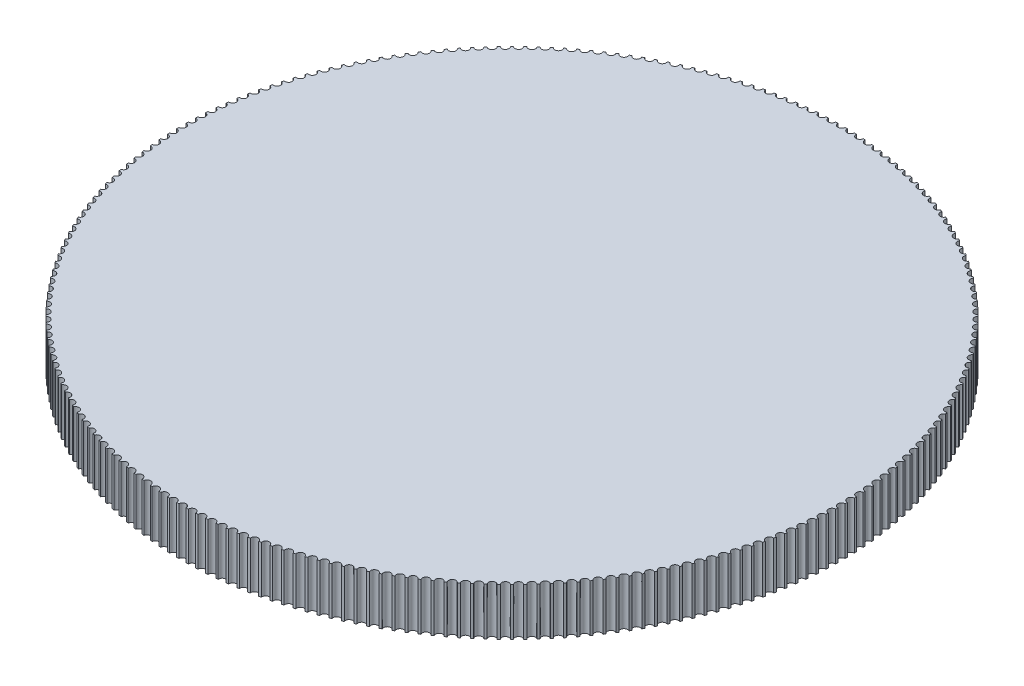
SolidWorks part; units mm, degrees
ref_plane "Front Plane" through (0, 0, 0) normal (0, 0, 1) x (1, 0, 0)
ref_plane "Top Plane" through (0, 0, 0) normal (0, 1, 0) x (1, 0, 0)
ref_plane "Right Plane" through (0, 0, 0) normal (1, 0, 0) x (0, 0, -1)
sketch "Sketch1" plane through (0, 0, 0) normal (0, 1, 0) x (1, 0, 0)
  line L0 (-69.255, 0) -> (69.255, 0) construction
  circle A0 centre (0, 0) radius 69.255
  dimension "D1" = 138.51
extrude "Boss-Extrude1" add sketch "Sketch1" along normal blind 10
sketch "Sketch2" plane through (0, 10, 0) normal (0, 1, 0) x (1, 0, 0)
  line L0 (0, 0) -> (69.255, 0) construction
  circle A0 centre (0, 0) radius 69.255 construction
  circle A1 centre (69.255, 0) radius 0.755
  circle A2 centre (69.2268, -1.9776) radius 0.755
  circle A3 centre (69.1421, -3.9537) radius 0.755
  circle A4 centre (69.001, -5.9265) radius 0.755
  circle A5 centre (68.8036, -7.8945) radius 0.755
  circle A6 centre (68.5501, -9.856) radius 0.755
  circle A7 centre (68.2407, -11.8095) radius 0.755
  circle A8 centre (67.8756, -13.7534) radius 0.755
  circle A9 centre (67.4552, -15.686) radius 0.755
  circle A10 centre (66.9798, -17.6059) radius 0.755
  circle A11 centre (66.4497, -19.5114) radius 0.755
  circle A12 centre (65.8654, -21.401) radius 0.755
  circle A13 centre (65.2274, -23.2731) radius 0.755
  circle A14 centre (64.5362, -25.1262) radius 0.755
  circle A15 centre (63.7924, -26.9589) radius 0.755
  circle A16 centre (62.9966, -28.7696) radius 0.755
  circle A17 centre (62.1493, -30.5568) radius 0.755
  circle A18 centre (61.2514, -32.319) radius 0.755
  circle A19 centre (60.3035, -34.055) radius 0.755
  circle A20 centre (59.3065, -35.7631) radius 0.755
  circle A21 centre (58.261, -37.4421) radius 0.755
  circle A22 centre (57.1681, -39.0905) radius 0.755
  circle A23 centre (56.0285, -40.7071) radius 0.755
  circle A24 centre (54.8432, -42.2904) radius 0.755
  circle A25 centre (53.6132, -43.8393) radius 0.755
  circle A26 centre (52.3394, -45.3524) radius 0.755
  circle A27 centre (51.023, -46.8285) radius 0.755
  circle A28 centre (49.665, -48.2664) radius 0.755
  circle A29 centre (48.2664, -49.665) radius 0.755
  circle A30 centre (46.8285, -51.023) radius 0.755
  circle A31 centre (45.3524, -52.3394) radius 0.755
  circle A32 centre (43.8393, -53.6132) radius 0.755
  circle A33 centre (42.2904, -54.8432) radius 0.755
  circle A34 centre (40.7071, -56.0285) radius 0.755
  circle A35 centre (39.0905, -57.1681) radius 0.755
  circle A36 centre (37.4421, -58.261) radius 0.755
  circle A37 centre (35.7631, -59.3065) radius 0.755
  circle A38 centre (34.055, -60.3035) radius 0.755
  circle A39 centre (32.319, -61.2514) radius 0.755
  circle A40 centre (30.5568, -62.1493) radius 0.755
  circle A41 centre (28.7696, -62.9966) radius 0.755
  circle A42 centre (26.9589, -63.7924) radius 0.755
  circle A43 centre (25.1262, -64.5362) radius 0.755
  circle A44 centre (23.2731, -65.2274) radius 0.755
  circle A45 centre (21.401, -65.8654) radius 0.755
  circle A46 centre (19.5114, -66.4497) radius 0.755
  circle A47 centre (17.6059, -66.9798) radius 0.755
  circle A48 centre (15.686, -67.4552) radius 0.755
  circle A49 centre (13.7534, -67.8756) radius 0.755
  circle A50 centre (11.8095, -68.2407) radius 0.755
  circle A51 centre (9.856, -68.5501) radius 0.755
  circle A52 centre (7.8945, -68.8036) radius 0.755
  circle A53 centre (5.9265, -69.001) radius 0.755
  circle A54 centre (3.9537, -69.1421) radius 0.755
  circle A55 centre (1.9776, -69.2268) radius 0.755
  circle A56 centre (0, -69.255) radius 0.755
  circle A57 centre (-1.9776, -69.2268) radius 0.755
  circle A58 centre (-3.9537, -69.1421) radius 0.755
  circle A59 centre (-5.9265, -69.001) radius 0.755
  circle A60 centre (-7.8945, -68.8036) radius 0.755
  circle A61 centre (-9.856, -68.5501) radius 0.755
  circle A62 centre (-11.8095, -68.2407) radius 0.755
  circle A63 centre (-13.7534, -67.8756) radius 0.755
  circle A64 centre (-15.686, -67.4552) radius 0.755
  circle A65 centre (-17.6059, -66.9798) radius 0.755
  circle A66 centre (-19.5114, -66.4497) radius 0.755
  circle A67 centre (-21.401, -65.8654) radius 0.755
  circle A68 centre (-23.2731, -65.2274) radius 0.755
  circle A69 centre (-25.1262, -64.5362) radius 0.755
  circle A70 centre (-26.9589, -63.7924) radius 0.755
  circle A71 centre (-28.7696, -62.9966) radius 0.755
  circle A72 centre (-30.5568, -62.1493) radius 0.755
  circle A73 centre (-32.319, -61.2514) radius 0.755
  circle A74 centre (-34.055, -60.3035) radius 0.755
  circle A75 centre (-35.7631, -59.3065) radius 0.755
  circle A76 centre (-37.4421, -58.261) radius 0.755
  circle A77 centre (-39.0905, -57.1681) radius 0.755
  circle A78 centre (-40.7071, -56.0285) radius 0.755
  circle A79 centre (-42.2904, -54.8432) radius 0.755
  circle A80 centre (-43.8393, -53.6132) radius 0.755
  circle A81 centre (-45.3524, -52.3394) radius 0.755
  circle A82 centre (-46.8285, -51.023) radius 0.755
  circle A83 centre (-48.2664, -49.665) radius 0.755
  circle A84 centre (-49.665, -48.2664) radius 0.755
  circle A85 centre (-51.023, -46.8285) radius 0.755
  circle A86 centre (-52.3394, -45.3524) radius 0.755
  circle A87 centre (-53.6132, -43.8393) radius 0.755
  circle A88 centre (-54.8432, -42.2904) radius 0.755
  circle A89 centre (-56.0285, -40.7071) radius 0.755
  circle A90 centre (-57.1681, -39.0905) radius 0.755
  circle A91 centre (-58.261, -37.4421) radius 0.755
  circle A92 centre (-59.3065, -35.7631) radius 0.755
  circle A93 centre (-60.3035, -34.055) radius 0.755
  circle A94 centre (-61.2514, -32.319) radius 0.755
  circle A95 centre (-62.1493, -30.5568) radius 0.755
  circle A96 centre (-62.9966, -28.7696) radius 0.755
  circle A97 centre (-63.7924, -26.9589) radius 0.755
  circle A98 centre (-64.5362, -25.1262) radius 0.755
  circle A99 centre (-65.2274, -23.2731) radius 0.755
  circle A100 centre (-65.8654, -21.401) radius 0.755
  circle A101 centre (-66.4497, -19.5114) radius 0.755
  circle A102 centre (-66.9798, -17.6059) radius 0.755
  circle A103 centre (-67.4552, -15.686) radius 0.755
  circle A104 centre (-67.8756, -13.7534) radius 0.755
  circle A105 centre (-68.2407, -11.8095) radius 0.755
  circle A106 centre (-68.5501, -9.856) radius 0.755
  circle A107 centre (-68.8036, -7.8945) radius 0.755
  circle A108 centre (-69.001, -5.9265) radius 0.755
  circle A109 centre (-69.1421, -3.9537) radius 0.755
  circle A110 centre (-69.2268, -1.9776) radius 0.755
  circle A111 centre (-69.255, 0) radius 0.755
  circle A112 centre (-69.2268, 1.9776) radius 0.755
  circle A113 centre (-69.1421, 3.9537) radius 0.755
  circle A114 centre (-69.001, 5.9265) radius 0.755
  circle A115 centre (-68.8036, 7.8945) radius 0.755
  circle A116 centre (-68.5501, 9.856) radius 0.755
  circle A117 centre (-68.2407, 11.8095) radius 0.755
  circle A118 centre (-67.8756, 13.7534) radius 0.755
  circle A119 centre (-67.4552, 15.686) radius 0.755
  circle A120 centre (-66.9798, 17.6059) radius 0.755
  circle A121 centre (-66.4497, 19.5114) radius 0.755
  circle A122 centre (-65.8654, 21.401) radius 0.755
  circle A123 centre (-65.2274, 23.2731) radius 0.755
  circle A124 centre (-64.5362, 25.1262) radius 0.755
  circle A125 centre (-63.7924, 26.9589) radius 0.755
  circle A126 centre (-62.9966, 28.7696) radius 0.755
  circle A127 centre (-62.1493, 30.5568) radius 0.755
  circle A128 centre (-61.2514, 32.319) radius 0.755
  circle A129 centre (-60.3035, 34.055) radius 0.755
  circle A130 centre (-59.3065, 35.7631) radius 0.755
  circle A131 centre (-58.261, 37.4421) radius 0.755
  circle A132 centre (-57.1681, 39.0905) radius 0.755
  circle A133 centre (-56.0285, 40.7071) radius 0.755
  circle A134 centre (-54.8432, 42.2904) radius 0.755
  circle A135 centre (-53.6132, 43.8393) radius 0.755
  circle A136 centre (-52.3394, 45.3524) radius 0.755
  circle A137 centre (-51.023, 46.8285) radius 0.755
  circle A138 centre (-49.665, 48.2664) radius 0.755
  circle A139 centre (-48.2664, 49.665) radius 0.755
  circle A140 centre (-46.8285, 51.023) radius 0.755
  circle A141 centre (-45.3524, 52.3394) radius 0.755
  circle A142 centre (-43.8393, 53.6132) radius 0.755
  circle A143 centre (-42.2904, 54.8432) radius 0.755
  circle A144 centre (-40.7071, 56.0285) radius 0.755
  circle A145 centre (-39.0905, 57.1681) radius 0.755
  circle A146 centre (-37.4421, 58.261) radius 0.755
  circle A147 centre (-35.7631, 59.3065) radius 0.755
  circle A148 centre (-34.055, 60.3035) radius 0.755
  circle A149 centre (-32.319, 61.2514) radius 0.755
  circle A150 centre (-30.5568, 62.1493) radius 0.755
  circle A151 centre (-28.7696, 62.9966) radius 0.755
  circle A152 centre (-26.9589, 63.7924) radius 0.755
  circle A153 centre (-25.1262, 64.5362) radius 0.755
  circle A154 centre (-23.2731, 65.2274) radius 0.755
  circle A155 centre (-21.401, 65.8654) radius 0.755
  circle A156 centre (-19.5114, 66.4497) radius 0.755
  circle A157 centre (-17.6059, 66.9798) radius 0.755
  circle A158 centre (-15.686, 67.4552) radius 0.755
  circle A159 centre (-13.7534, 67.8756) radius 0.755
  circle A160 centre (-11.8095, 68.2407) radius 0.755
  circle A161 centre (-9.856, 68.5501) radius 0.755
  circle A162 centre (-7.8945, 68.8036) radius 0.755
  circle A163 centre (-5.9265, 69.001) radius 0.755
  circle A164 centre (-3.9537, 69.1421) radius 0.755
  circle A165 centre (-1.9776, 69.2268) radius 0.755
  circle A166 centre (0, 69.255) radius 0.755
  circle A167 centre (1.9776, 69.2268) radius 0.755
  circle A168 centre (3.9537, 69.1421) radius 0.755
  circle A169 centre (5.9265, 69.001) radius 0.755
  circle A170 centre (7.8945, 68.8036) radius 0.755
  circle A171 centre (9.856, 68.5501) radius 0.755
  circle A172 centre (11.8095, 68.2407) radius 0.755
  circle A173 centre (13.7534, 67.8756) radius 0.755
  circle A174 centre (15.686, 67.4552) radius 0.755
  circle A175 centre (17.6059, 66.9798) radius 0.755
  circle A176 centre (19.5114, 66.4497) radius 0.755
  circle A177 centre (21.401, 65.8654) radius 0.755
  circle A178 centre (23.2731, 65.2274) radius 0.755
  circle A179 centre (25.1262, 64.5362) radius 0.755
  circle A180 centre (26.9589, 63.7924) radius 0.755
  circle A181 centre (28.7696, 62.9966) radius 0.755
  circle A182 centre (30.5568, 62.1493) radius 0.755
  circle A183 centre (32.319, 61.2514) radius 0.755
  circle A184 centre (34.055, 60.3035) radius 0.755
  circle A185 centre (35.7631, 59.3065) radius 0.755
  circle A186 centre (37.4421, 58.261) radius 0.755
  circle A187 centre (39.0905, 57.1681) radius 0.755
  circle A188 centre (40.7071, 56.0285) radius 0.755
  circle A189 centre (42.2904, 54.8432) radius 0.755
  circle A190 centre (43.8393, 53.6132) radius 0.755
  circle A191 centre (45.3524, 52.3394) radius 0.755
  circle A192 centre (46.8285, 51.023) radius 0.755
  circle A193 centre (48.2664, 49.665) radius 0.755
  circle A194 centre (49.665, 48.2664) radius 0.755
  circle A195 centre (51.023, 46.8285) radius 0.755
  circle A196 centre (52.3394, 45.3524) radius 0.755
  circle A197 centre (53.6132, 43.8393) radius 0.755
  circle A198 centre (54.8432, 42.2904) radius 0.755
  circle A199 centre (56.0285, 40.7071) radius 0.755
  circle A200 centre (57.1681, 39.0905) radius 0.755
  circle A201 centre (58.261, 37.4421) radius 0.755
  circle A202 centre (59.3065, 35.7631) radius 0.755
  circle A203 centre (60.3035, 34.055) radius 0.755
  circle A204 centre (61.2514, 32.319) radius 0.755
  circle A205 centre (62.1493, 30.5568) radius 0.755
  circle A206 centre (62.9966, 28.7696) radius 0.755
  circle A207 centre (63.7924, 26.9589) radius 0.755
  circle A208 centre (64.5362, 25.1262) radius 0.755
  circle A209 centre (65.2274, 23.2731) radius 0.755
  circle A210 centre (65.8654, 21.401) radius 0.755
  circle A211 centre (66.4497, 19.5114) radius 0.755
  circle A212 centre (66.9798, 17.6059) radius 0.755
  circle A213 centre (67.4552, 15.686) radius 0.755
  circle A214 centre (67.8756, 13.7534) radius 0.755
  circle A215 centre (68.2407, 11.8095) radius 0.755
  circle A216 centre (68.5501, 9.856) radius 0.755
  circle A217 centre (68.8036, 7.8945) radius 0.755
  circle A218 centre (69.001, 5.9265) radius 0.755
  circle A219 centre (69.1421, 3.9537) radius 0.755
  circle A220 centre (69.2268, 1.9776) radius 0.755
  point P7 (0, 0)
  point P8 (0, 0)
  point P9 (0, 0)
  point P448 (0, 0)
  point P449 (0, 0)
  dimension "D1" = 1.51
  dimension "D2" = 220
extrude "Cut-Extrude2" cut sketch "Sketch2" against normal up to surface (10 mm away) up to face at (0, 0, 69.255)
